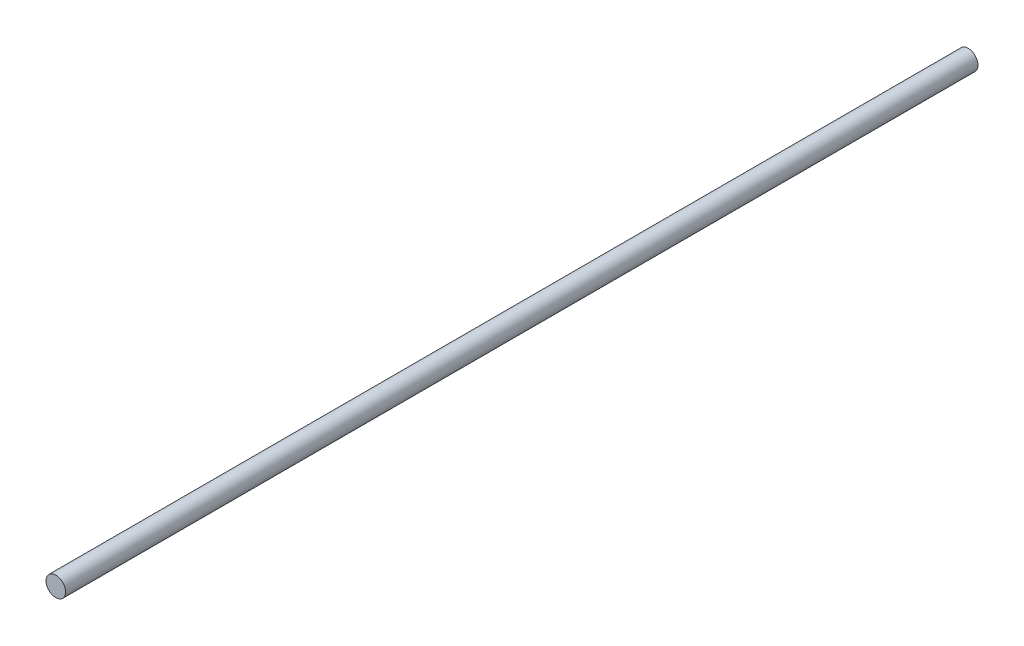
SolidWorks part; units mm, degrees
material "Chrome Stainless Steel"
ref_plane "Front Plane" through (0, 0, 0) normal (0, 0, 1) x (1, 0, 0)
ref_plane "Top Plane" through (0, 0, 0) normal (0, 1, 0) x (1, 0, 0)
ref_plane "Right Plane" through (0, 0, 0) normal (1, 0, 0) x (0, 0, -1)
sketch "Sketch1" plane through (0, 0, 0) normal (0, 0, 1) x (1, 0, 0)
  circle A0 centre (0, 0) radius 3
extrude "Boss-Extrude1" add sketch "Sketch1" along normal blind 279.4
